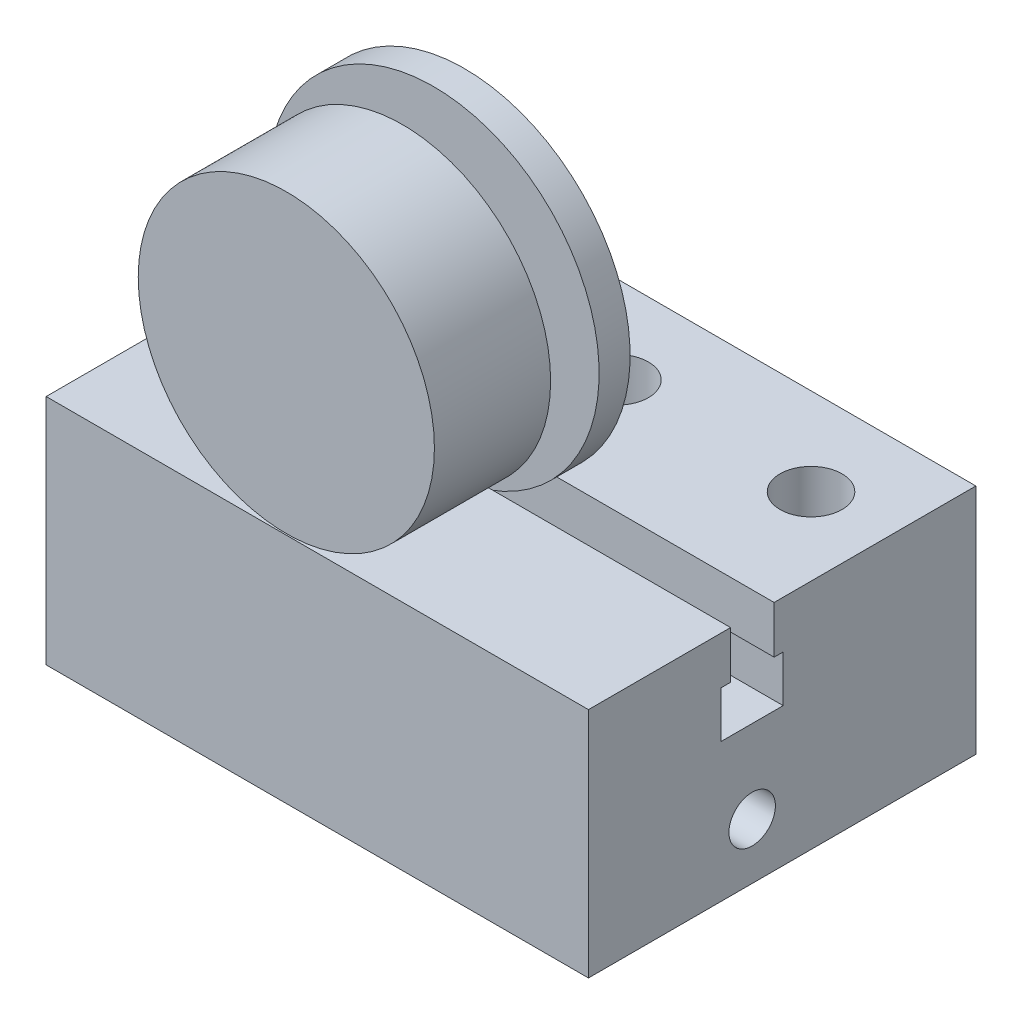
SolidWorks part; units mm, degrees
ref_plane "Front Plane" through (0, 0, 0) normal (0, 0, 1) x (1, 0, 0)
ref_plane "Top Plane" through (0, 0, 0) normal (0, 1, 0) x (1, 0, 0)
ref_plane "Right Plane" through (0, 0, 0) normal (1, 0, 0) x (0, 0, -1)
sketch "Sketch1" plane through (0, 0, 0) normal (0, 1, 0) x (1, 0, 0)
  line L1 (10.255, 44.7419) -> (80.255, 44.7419)
  line L2 (10.255, 44.7419) -> (10.255, -5.2581)
  line L3 (10.255, -5.2581) -> (80.255, -5.2581)
  line L4 (80.255, 44.7419) -> (80.255, -5.2581)
  circle A0 centre (45.255, 33.4759) radius 4
  circle A1 centre (70.255, 33.4668) radius 4
  circle A2 centre (20.255, 33.4678) radius 4
  dimension "D3" = 25
  dimension "D1" = 70
  dimension "D2" = 50
  dimension "D4" = 25
extrude "Boss-Extrude1" add sketch "Sketch1" along normal blind 30
sketch "Sketch2" plane through (10.255, 0, 0) normal (-1, 0, 0) x (0, 0, 1)
  line L3 (-19.8706, 17.881) -> (-11.8706, 17.881)
  line L4 (-11.8706, 23.881) -> (-11.8706, 17.881)
  line L9 (-19.8706, 17.881) -> (-19.8706, 23.881)
  line L10 (-19.8706, 23.881) -> (-18.7033, 23.881)
  line L11 (-18.7033, 23.881) -> (-18.7033, 30)
  line L13 (-13.0867, 30) -> (-13.0867, 23.881)
  line L14 (-13.0867, 23.881) -> (-11.8706, 23.881)
  line L15 (-44.7419, 30) -> (5.2581, 30) construction
  line L16 (-18.7033, 30) -> (-13.0867, 30)
  circle A0 centre (-15.8706, 7.1987) radius 3
  dimension "D1" = 6
  dimension "D2" = 8
extrude "Cut-Extrude1" cut sketch "Sketch2" against normal blind 71
sketch "Sketch6" plane through (0, 0, 5.2581) normal (0, 0, 1) x (1, 0, 0)
  circle A0 centre (41.255, 49.2849) radius 19.1151
  point P2 (0, 0)
extrude "Boss-Extrude3" add sketch "Sketch6" against normal blind 15 separate body
sketch "Sketch7" plane through (0, 0, -9.7419) normal (0, 0, -1) x (-1, 0, 0)
  circle A0 centre (-41.255, 49.2849) radius 2
extrude "Boss-Extrude4" add sketch "Sketch7" along normal blind 4
sketch "Sketch8" plane through (0, 0, -13.7419) normal (0, 0, -1) x (-1, 0, 0)
  circle A0 centre (-41.255, 49.2849) radius 21.3745
extrude "Boss-Extrude5" add sketch "Sketch8" along normal blind 4 contours A0
